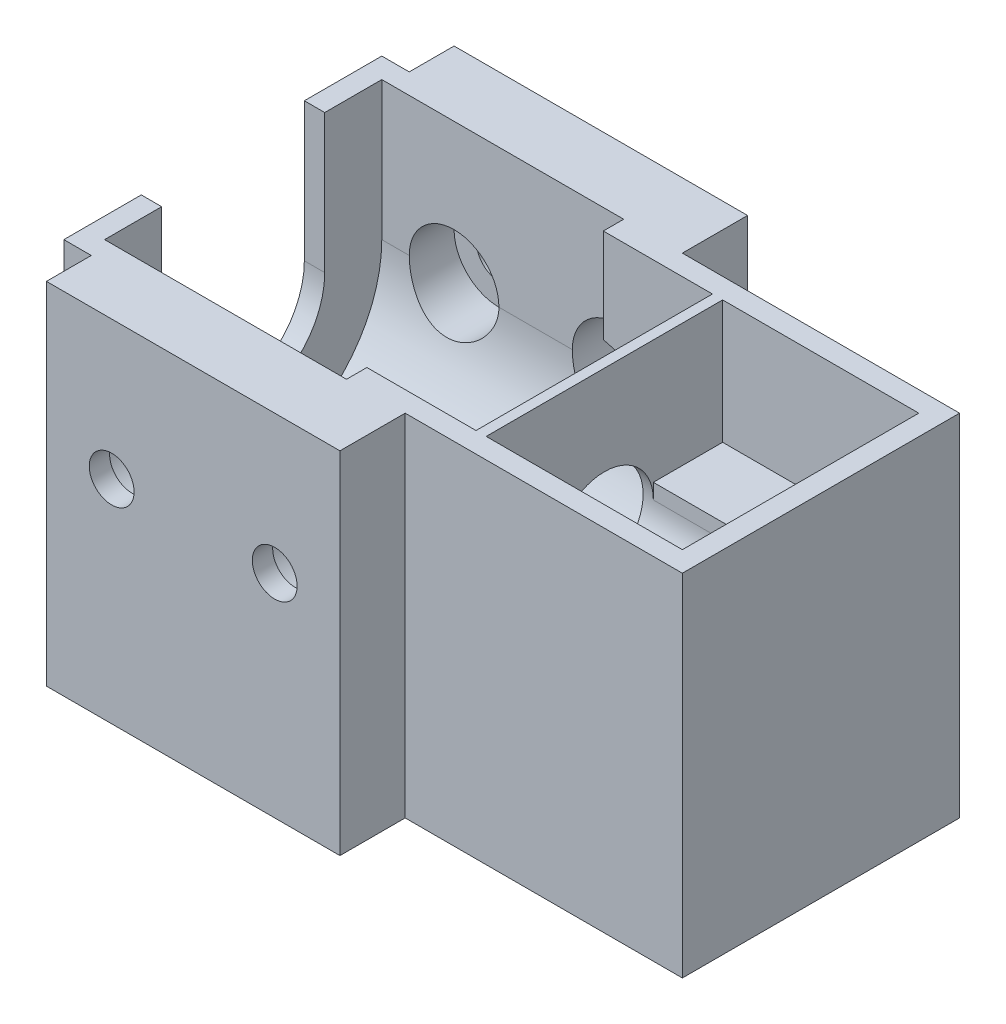
SolidWorks part; units mm, degrees
ref_plane "Front Plane" through (0, 0, 0) normal (0, 0, 1) x (1, 0, 0)
ref_plane "Top Plane" through (0, 0, 0) normal (0, 1, 0) x (1, 0, 0)
ref_plane "Right Plane" through (0, 0, 0) normal (1, 0, 0) x (0, 0, -1)
sketch "Sketch1" plane through (0, 0, 0) normal (0, 0, 1) x (1, 0, 0)
  line L1 (-76.2, -50.8) -> (40.64, -50.8)
  line L2 (-76.2, -50.8) -> (-76.2, 0)
  line L3 (-76.2, 0) -> (40.64, 0)
  line L4 (40.64, -50.8) -> (40.64, 0)
  line L5 (-76.2, -50.8) -> (40.64, 0) construction
  line L6 (-76.2, 0) -> (40.64, -50.8) construction
  point P0 (0, 0)
  dimension "D1" = 116.84
  dimension "D2" = 50.8
  dimension "D3" = 76.2
extrude "Boss-Extrude1" add sketch "Sketch1" along normal mid plane 63.5
sketch "Sketch2" plane through (0, 0, 0) normal (0, 0, 1) x (1, 0, 0)
  line L0 (-152.4829, -25.4) -> (6, -25.4) construction
  line L1 (-49.3609, -3.81) -> (-49.3609, -12.7)
  line L2 (40.64, 0) -> (-76.2, 0) construction
  line L3 (40.64, 0) -> (-76.2, 0) construction
  line L4 (-11.68, -3.81) -> (-11.68, -6.985)
  line L5 (-11.68, -25.4) -> (-11.68, -3.81) construction
  line L6 (-128.4172, -25.4) -> (-157.8092, -25.4)
  line L7 (6, -25.4) -> (40.64, -25.4)
  line L8 (-607.3619, -25.4) -> (6, -25.4) construction
  line L9 (-49.3609, -3.81) -> (-11.68, -3.81)
  line L10 (6, -25.4) -> (-128.4172, -25.4)
  line L11 (-11.68, -6.985) -> (5.32, -6.985)
  line L12 (5.32, -6.985) -> (5.32, -17.78)
  line L13 (5.32, -17.78) -> (23.32, -17.78)
  line L14 (-49.3609, -12.7) -> (-220.2024, -12.7)
  line L15 (-220.2024, -12.7) -> (-220.2024, -25.4)
  line L16 (-220.2024, -25.4) -> (-157.8092, -25.4)
  line L17 (23.32, -17.78) -> (23.32, -25.4) construction
  line L18 (23.32, -17.78) -> (40.64, -17.78)
  line L19 (40.64, -50.8) -> (40.64, 0) construction
  line L20 (40.64, -17.78) -> (40.64, -25.4)
  line L21 (-76.2, 0) -> (-76.2, -50.8) construction
  point P23 (-11.68, -25.4)
  dimension "D1" = 21.59
  dimension "D2" = 37.6809
  dimension "D3" = 25.4
  dimension "D4" = 35
  dimension "D5" = 7.62
  dimension "D6" = 3.175
  dimension "D7" = 26.8391
  dimension "D8" = 18
  dimension "D9" = 12.7
revolve "Cut-Revolve1" cut sketch "Sketch2" angle 360 about L0
sketch "Sketch38" plane through (40.64, 0, 0) normal (1, 0, 0) x (0, 0, -1)
  line L1 (-10, -35.4) -> (10, -35.4)
  line L2 (-10, -35.4) -> (-10, -15.4)
  line L3 (-10, -15.4) -> (10, -15.4)
  line L4 (10, -35.4) -> (10, -15.4)
  line L5 (-10, -35.4) -> (10, -15.4) construction
  line L6 (-10, -15.4) -> (10, -35.4) construction
  point P0 (0, -25.4)
  point P1 (0, -25.4)
  dimension "D1" = 20
  dimension "D2" = 20
extrude "Cut-Extrude33" cut sketch "Sketch38" against normal offset from surface (33.7325 mm away) 1.5875 up to face at (5.32, -43.815, 0)
sketch "Sketch37" plane through (40.64, 0, 0) normal (1, 0, 0) x (0, 0, -1)
  line L0 (31.75, -50.8) -> (31.75, 0) construction
  line L1 (-31.75, 0) -> (31.75, 0)
  line L2 (-31.75, 0) -> (-31.75, -25.4)
  line L3 (-31.75, -25.4) -> (31.75, -25.4)
  line L4 (31.75, 0) -> (31.75, -25.4)
  line L5 (10, -35.4) -> (10, -15.4) construction
  point P7 (0, -25.4)
  point P11 (0, 0)
  point P14 (10, -25.4)
extrude "Cut-Extrude32" cut sketch "Sketch37" against normal through all
sketch "Sketch39" plane through (0, -25.4, 0) normal (0, 1, 0) x (1, 0, 0)
  line L10 (-76.2, 12.7) -> (-49.3609, 12.7)
  line L11 (-49.3609, 12.7) -> (-49.3609, 21.59)
  line L12 (-49.3609, 21.59) -> (-11.68, 21.59)
  line L13 (-11.68, 21.59) -> (-11.68, 18.415)
  line L14 (-11.68, 18.415) -> (5.32, 18.415)
  line L15 (5.32, 18.415) -> (5.32, 7.62)
  line L16 (5.32, 18.415) -> (5.32, 7.62)
  line L17 (40.64, 10) -> (40.64, 31.75)
  line L18 (40.64, 31.75) -> (-76.2, 31.75)
  line L19 (-76.2, 31.75) -> (-76.2, 12.7)
  line L20 (-76.2, 12.7) -> (-49.3609, 12.7)
  line L21 (-49.3609, 12.7) -> (-49.3609, 21.59)
  line L22 (-49.3609, 21.59) -> (-11.68, 21.59)
  line L23 (-11.68, 21.59) -> (-11.68, 18.415)
  line L24 (-11.68, 18.415) -> (5.32, 18.415)
  line L25 (6.9075, 10) -> (40.64, 10)
  line L26 (6.9075, 10) -> (40.64, 10)
  line L27 (40.64, 10) -> (40.64, 31.75)
  line L28 (40.64, 31.75) -> (-76.2, 31.75)
  line L29 (-76.2, 31.75) -> (-76.2, 12.7)
  line L30 (-49.3609, -12.7) -> (-76.2, -12.7)
  line L31 (-76.2, -12.7) -> (-76.2, -31.75)
  line L32 (-76.2, -31.75) -> (40.64, -31.75)
  line L33 (40.64, -31.75) -> (40.64, -10)
  line L34 (40.64, -10) -> (6.9075, -10)
  line L35 (40.64, -10) -> (6.9075, -10)
  line L36 (5.32, -18.415) -> (-11.68, -18.415)
  line L37 (-11.68, -18.415) -> (-11.68, -21.59)
  line L38 (-11.68, -21.59) -> (-49.3609, -21.59)
  line L39 (-49.3609, -21.59) -> (-49.3609, -12.7)
  line L40 (-49.3609, -12.7) -> (-76.2, -12.7)
  line L41 (-76.2, -12.7) -> (-76.2, -31.75)
  line L42 (-76.2, -31.75) -> (40.64, -31.75)
  line L43 (40.64, -31.75) -> (40.64, -10)
  line L44 (5.32, -7.62) -> (5.32, -18.415)
  line L45 (5.32, -7.62) -> (5.32, -18.415)
  line L46 (5.32, -18.415) -> (-11.68, -18.415)
  line L47 (-11.68, -18.415) -> (-11.68, -21.59)
  line L48 (-11.68, -21.59) -> (-49.3609, -21.59)
  line L49 (-49.3609, -21.59) -> (-49.3609, -12.7)
  line L52 (5.32, 7.62) -> (6.9075, 7.62)
  line L53 (5.32, 7.62) -> (6.9075, 7.62)
  line L54 (6.9075, 7.62) -> (6.9075, 10)
  line L55 (6.9075, 7.62) -> (6.9075, 10)
  line L56 (6.9075, -10) -> (6.9075, -7.62)
  line L57 (6.9075, -10) -> (6.9075, -7.62)
  line L58 (6.9075, -7.62) -> (5.32, -7.62)
  line L59 (6.9075, -7.62) -> (5.32, -7.62)
  dimension "D1" = 0
  dimension "D2" = 0
extrude "Boss-Extrude5" add sketch "Sketch39" along normal blind 25.4
sketch "Sketch40" plane through (0, 0, 0) normal (0, 1, 0) x (1, 0, 0)
  line L0 (6.9075, 10) -> (40.64, 10) construction
  line L1 (23.32, 10) -> (40.64, 10)
  line L2 (23.32, 10) -> (23.32, -10)
  line L3 (23.32, -10) -> (40.64, -10)
  line L4 (40.64, 10) -> (40.64, -10)
  line L6 (-11.68, 21.59) -> (-11.68, 18.415) construction
  dimension "D1" = 35
extrude "Boss-Extrude6" add sketch "Sketch40" against normal up to next
sketch "Sketch41" plane through (0, 0, 0) normal (0, 1, 0) x (1, 0, 0)
  line L2 (-76.2, 12.7) -> (-76.2, -12.7) construction
  circle A0 centre (-57.15, 0) radius 3.1134
  circle A1 centre (-31.75, 0) radius 3.1134
  circle A2 centre (-6.35, 0) radius 3.1134
  dimension "D1" = 19.05
extrude "Cut-Extrude34" cut sketch "Sketch41" against normal through all
ref_plane "Plane_Mid" through (0, -25.4, 0) normal (0, 1, 0) x (1, 0, 0)
ref_axis "Axis1" through (6.9075, -25.4, 0) along (-1, 0, 0)
sketch "Sketch42" plane through (0, 0, 0) normal (0, 0, 1) x (1, 0, 0)
  line L0 (1.7462, -25.4) -> (-1.7462, -25.4) construction
  line L1 (-76.2, 0) -> (-76.2, -25.4) construction
  circle A0 centre (-38.1, -25.4) radius 3.4925
  circle A1 centre (-12.7, -25.4) radius 3.4925
  dimension "D1" = 6.985
  dimension "D2" = 38.1
extrude "Cut-Extrude35" cut sketch "Sketch42" against normal through all both and the other way through all
sketch "Sketch43" plane through (0, 0, 0) normal (0, 0, 1) x (1, 0, 0)
  circle A0 centre (-38.1, -25.4) radius 6.985
  circle A1 centre (-12.7, -25.4) radius 6.985
  dimension "D1" = 13.97
extrude "Cut-Extrude36" cut sketch "Sketch43" against normal offset from surface (28.575 mm away) 3.175 up to face at (-9.2075, -25.4, -31.75)
extrude "Cut-Extrude37" cut sketch "Sketch43<2>" along normal offset from surface (28.575 mm away) 3.175 up to face at (-9.2075, -25.4, 31.75)
sketch "Sketch43<2>" plane through (0, 0, 0) normal (0, 0, 1) x (1, 0, 0) same geometry as "Sketch43"
sketch "Sketch44" plane through (0, 0, 0) normal (0, 1, 0) x (1, 0, 0)
  line L0 (5.32, -18.415) -> (-11.68, -18.415) construction
  line L1 (6.9075, 18.415) -> (22.82, 18.415)
  line L2 (6.9075, 18.415) -> (6.9075, -18.415)
  line L3 (6.9075, -18.415) -> (22.82, -18.415)
  line L4 (22.82, 18.415) -> (22.82, -18.415)
  line L5 (-11.68, 18.415) -> (5.32, 18.415) construction
  line L6 (6.9075, 7.62) -> (6.9075, 10) construction
  line L7 (23.32, 10) -> (23.32, -10) construction
  dimension "D1" = 0.5
extrude "Cut-Extrude38" cut sketch "Sketch44" against normal up to surface (35.4 mm away) up to face at (15.1138, -35.4, 0)
sketch "Sketch45" plane through (0, 0, 0) normal (0, 0, 1) x (1, 0, 0)
  line L0 (40.64, 0) -> (-76.2, 0) construction
  line L2 (37.465, 0) -> (22.82, 0)
  line L4 (37.465, 0) -> (37.465, -15.4)
  line L5 (37.465, -15.4) -> (22.82, -15.4)
  line L8 (22.82, 0) -> (22.82, -15.4)
  line L9 (40.64, -50.8) -> (40.64, 0) construction
  line L10 (22.82, -35.4) -> (22.82, 0) construction
  line L11 (-5.715, -25.4) -> (5.32, -25.4) construction
  dimension "D1" = 3.175
  dimension "D2" = 10
extrude "Cut-Extrude39" cut sketch "Sketch45" against normal up to surface and the other way up to surface up to face at (14.8637, -17.7, -18.415) other way up to face at (14.8638, -17.7, 18.415)
sketch "Sketch46" plane through (0, 0, 0) normal (0, 1, 0) x (1, 0, 0)
  line L0 (-11.68, 18.415) -> (5.32, 18.415) construction
  line L1 (40.64, 31.75) -> (-2.54, 31.75)
  line L2 (40.64, 31.75) -> (40.64, 21.59)
  line L3 (40.64, 21.59) -> (-2.54, 21.59)
  line L4 (-2.54, 31.75) -> (-2.54, 21.59)
  line L5 (-76.2, 0) -> (40.64, 0) construction
  line L6 (-76.2, 12.7) -> (-76.2, -12.7) construction
  line L7 (40.64, -31.75) -> (40.64, 31.75) construction
  line L8 (40.64, -31.75) -> (40.64, -21.59)
  line L9 (40.64, -21.59) -> (-2.54, -21.59)
  line L10 (40.64, -31.75) -> (-2.54, -31.75)
  line L11 (-2.54, -31.75) -> (-2.54, -21.59)
  line L12 (-49.3609, 21.59) -> (-11.68, 21.59) construction
  line L13 (-76.2, 31.75) -> (-48.26, 31.75)
  line L14 (-76.2, 31.75) -> (-76.2, 24.765)
  line L15 (-76.2, 24.765) -> (-48.26, 24.765)
  line L16 (-48.26, 31.75) -> (-48.26, 24.765)
  line L17 (-48.26, -31.75) -> (-48.26, -24.765)
  line L18 (-76.2, -24.765) -> (-48.26, -24.765)
  line L19 (-76.2, -31.75) -> (-76.2, -24.765)
  line L20 (-76.2, -31.75) -> (-48.26, -31.75)
  dimension "D1" = 3.175
  dimension "D2" = 3.175
  dimension "D3" = 3.175
  dimension "D4" = 3.175
extrude "Cut-Extrude40" cut sketch "Sketch46" against normal through all
sketch "Sketch49" plane through (0, 0, 0) normal (0, 1, 0) x (1, 0, 0)
  line L0 (-48.26, -24.765) -> (-76.2, -24.765) construction
  line L1 (-76.2, 24.765) -> (-52.5359, 24.765)
  line L2 (-76.2, 24.765) -> (-76.2, -24.765)
  line L3 (-76.2, -24.765) -> (-52.5359, -24.765)
  line L4 (-52.5359, 24.765) -> (-52.5359, -24.765)
  line L5 (-49.3609, -21.59) -> (-49.3609, 21.59) construction
  dimension "D1" = 3.175
extrude "Cut-Extrude42" cut sketch "Sketch49" against normal through all
sketch "Sketch50" plane through (0, 0, 0) normal (0, 1, 0) x (1, 0, 0)
  line L0 (-2.54, 21.59) -> (40.64, 21.59) construction
  line L1 (22.566, 20.066) -> (22.82, 20.066)
  line L2 (22.566, 20.066) -> (22.566, 21.59)
  line L3 (22.566, 21.59) -> (22.82, 21.59)
  line L4 (22.82, 20.066) -> (22.82, 21.59)
  line L5 (22.693, 21.59) -> (22.693, 20.066) construction
  line L6 (22.566, 20.828) -> (22.82, 20.828) construction
  line L8 (22.82, 10) -> (22.82, 18.415) construction
  line L9 (21.042, 20.066) -> (21.296, 20.066)
  line L10 (21.296, 20.066) -> (21.296, 21.59)
  line L11 (21.042, 21.59) -> (21.296, 21.59)
  line L12 (21.042, 20.066) -> (21.042, 21.59)
  line L13 (19.518, 20.066) -> (19.772, 20.066)
  line L14 (19.772, 20.066) -> (19.772, 21.59)
  line L15 (19.518, 21.59) -> (19.772, 21.59)
  line L16 (19.518, 20.066) -> (19.518, 21.59)
  line L17 (17.994, 20.066) -> (18.248, 20.066)
  line L18 (18.248, 20.066) -> (18.248, 21.59)
  line L19 (17.994, 21.59) -> (18.248, 21.59)
  line L20 (17.994, 20.066) -> (17.994, 21.59)
  line L21 (16.47, 20.066) -> (16.724, 20.066)
  line L22 (16.724, 20.066) -> (16.724, 21.59)
  line L23 (16.47, 21.59) -> (16.724, 21.59)
  line L24 (16.47, 20.066) -> (16.47, 21.59)
  line L25 (14.946, 20.066) -> (15.2, 20.066)
  line L26 (15.2, 20.066) -> (15.2, 21.59)
  line L27 (14.946, 21.59) -> (15.2, 21.59)
  line L28 (14.946, 20.066) -> (14.946, 21.59)
  line L29 (13.422, 20.066) -> (13.676, 20.066)
  line L30 (13.676, 20.066) -> (13.676, 21.59)
  line L31 (13.422, 21.59) -> (13.676, 21.59)
  line L32 (13.422, 20.066) -> (13.422, 21.59)
  line L33 (11.898, 20.066) -> (12.152, 20.066)
  line L34 (12.152, 20.066) -> (12.152, 21.59)
  line L35 (11.898, 21.59) -> (12.152, 21.59)
  line L36 (11.898, 20.066) -> (11.898, 21.59)
  line L37 (10.374, 20.066) -> (10.628, 20.066)
  line L38 (10.628, 20.066) -> (10.628, 21.59)
  line L39 (10.374, 21.59) -> (10.628, 21.59)
  line L40 (10.374, 20.066) -> (10.374, 21.59)
  line L41 (8.85, 20.066) -> (9.104, 20.066)
  line L42 (9.104, 20.066) -> (9.104, 21.59)
  line L43 (8.85, 21.59) -> (9.104, 21.59)
  line L44 (8.85, 20.066) -> (8.85, 21.59)
  point P0 (22.693, 20.828)
  dimension "D1" = 0.254
  dimension "D2" = 1.524
  dimension "D3" = 10
extrude "Cut-Extrude43" cut sketch "Sketch50" against normal blind 2.54
sketch "Sketch52" plane through (23.32, 0, 0) normal (-1, 0, 0) x (0, 0, 1)
  circle A0 centre (0, -25.4) radius 0.3175
  dimension "D1" = 0.635
extrude "Cut-Extrude45" cut sketch "Sketch52" against normal blind 0.0508
sketch "Sketch53" plane through (23.32, 0, 0) normal (-1, 0, 0) x (0, 0, 1)
  circle A0 centre (0, -25.4) radius 2
  dimension "D1" = 4
extrude "Cut-Extrude46" cut sketch "Sketch53" against normal blind 0.0254
sketch "Sketch54" plane through (0, -35.4, 0) normal (0, 1, 0) x (1, 0, 0)
  line L0 (22.82, 10) -> (22.82, -10)
  line L8 (23.32, 10) -> (22.82, 10)
  line L9 (22.82, 10) -> (22.82, 18.415)
  line L10 (22.82, 18.415) -> (6.9075, 18.415)
  line L11 (6.9075, 18.415) -> (6.9075, -18.415)
  line L12 (6.9075, -18.415) -> (22.82, -18.415)
  line L13 (22.82, -18.415) -> (22.82, -10)
  line L14 (22.82, -10) -> (23.32, -10)
  line L15 (23.32, -10) -> (23.32, 10)
  line L17 (22.82, 10) -> (22.82, 18.415)
  line L18 (22.82, 18.415) -> (6.9075, 18.415)
  line L19 (6.9075, 18.415) -> (6.9075, -18.415)
  line L20 (6.9075, -18.415) -> (22.82, -18.415)
  line L21 (22.82, -18.415) -> (22.82, -10)
  dimension "D1" = 0
extrude "Boss-Extrude7" add sketch "Sketch54" along normal blind 2.54
sketch "Sketch55" plane through (0, -32.86, 0) normal (0, 1, 0) x (1, 0, 0)
  line L0 (22.82, -18.415) -> (22.82, -10) construction
  line L1 (22.82, 10) -> (6.9075, 10)
  line L2 (22.82, 10) -> (22.82, 18.415)
  line L3 (22.82, 18.415) -> (6.9075, 18.415)
  line L4 (6.9075, 10) -> (6.9075, 18.415)
  line L5 (22.82, 10) -> (6.9075, 18.415) construction
  line L6 (22.82, 18.415) -> (6.9075, 10) construction
  line L7 (6.9075, -18.415) -> (22.82, -18.415)
  line L8 (6.9075, -18.415) -> (6.9075, -10)
  line L9 (6.9075, -10) -> (22.82, -10)
  line L10 (22.82, -18.415) -> (22.82, -10)
  line L11 (6.9075, -18.415) -> (22.82, -10) construction
  line L12 (6.9075, -10) -> (22.82, -18.415) construction
  point P4 (14.8637, 14.2075)
  point P5 (0, 0)
  point P11 (14.8637, -14.2075)
  point P15 (0, 0)
  point P17 (0, 0)
extrude "Boss-Extrude8" add sketch "Sketch55" along normal up to surface (17.46 mm away) up to face at (26.6063, -15.4, 0)
sketch "Sketch56" plane through (0, 0, 0) normal (0, 0, 1) x (1, 0, 0)
  line L0 (16.47, -27.4) -> (16.47, -32.86) construction
  line L1 (23.3454, -27.4) -> (16.47, -27.4) construction
  line L2 (23.3454, -23.4) -> (23.3454, -27.4) construction
  line L3 (6.9075, -25.4) -> (5.32, -25.4) construction
  line L4 (6.9075, -32.86) -> (6.9075, -25.4) construction
  line L5 (11.6888, -30.13) -> (6.9075, -30.13) construction
  line L6 (11.6888, -30.13) -> (16.47, -30.13) construction
  line L7 (16.47, -27.4) -> (22.82, -27.4)
  line L8 (22.82, -27.4) -> (22.82, -32.86)
  line L9 (6.9075, -32.86) -> (22.82, -32.86)
  spline S0 degree 3 poles (6.9075, -32.86) (7.8397, -32.86) (14.8054, -27.986) (15.1522, -27.4) (16.47, -27.4) knots 0 0 0 0 0.327131 1 1 1 1
  point P6 (16.47, -30.13)
  point P8 (0, 0)
  point P11 (6.9075, -32.86)
  dimension "D1" = 2
  dimension "D2" = 6.35
extrude "Boss-Extrude9" add sketch "Sketch56" along normal up to next and the other way up to next
sketch "Sketch57" plane through (0, -15.4, 0) normal (0, 1, 0) x (1, 0, 0)
  line L8 (23.32, -10) -> (6.9075, -10)
  line L9 (6.9075, -10) -> (6.9075, -18.415)
  line L10 (6.9075, -18.415) -> (37.465, -18.415)
  line L11 (37.465, -18.415) -> (37.465, 18.415)
  line L12 (37.465, 18.415) -> (6.9075, 18.415)
  line L13 (23.32, -10) -> (6.9075, -10)
  line L14 (6.9075, 18.415) -> (6.9075, 10)
  line L15 (23.32, 10) -> (23.32, -10)
  line L16 (6.9075, 18.415) -> (6.9075, 10)
  line L17 (6.9075, -10) -> (6.9075, -18.415)
  line L18 (6.9075, -18.415) -> (37.465, -18.415)
  line L19 (37.465, -18.415) -> (37.465, 18.415)
  line L20 (37.465, 18.415) -> (6.9075, 18.415)
  line L21 (6.9075, 10) -> (23.32, 10)
  line L22 (6.9075, 10) -> (23.32, 10)
  line L23 (23.32, 10) -> (23.32, -10)
  dimension "D1" = 0
extrude "Cut-Extrude47" cut sketch "Sketch57" against normal blind 7.62
sketch "Sketch58" plane through (0, -50.8, 0) normal (0, -1, 0) x (1, 0, 0)
  line L12 (-48.26, 24.765) -> (-52.5359, 24.765)
  line L13 (-52.5359, 24.765) -> (-52.5359, -24.765)
  line L14 (-52.5359, -24.765) -> (-48.26, -24.765)
  line L15 (-48.26, -24.765) -> (-48.26, -31.75)
  line L16 (-48.26, -31.75) -> (-2.54, -31.75)
  line L17 (-2.54, -31.75) -> (-2.54, -21.59)
  line L18 (-2.54, -21.59) -> (40.64, -21.59)
  line L19 (40.64, -21.59) -> (40.64, 21.59)
  line L20 (40.64, 21.59) -> (-2.54, 21.59)
  line L21 (-2.54, 21.59) -> (-2.54, 31.75)
  line L22 (-2.54, 31.75) -> (-48.26, 31.75)
  line L23 (-48.26, 31.75) -> (-48.26, 24.765)
  line L24 (-48.26, 24.765) -> (-52.5359, 24.765)
  line L25 (-52.5359, 24.765) -> (-52.5359, -24.765)
  line L26 (-52.5359, -24.765) -> (-48.26, -24.765)
  line L27 (-48.26, -24.765) -> (-48.26, -31.75)
  line L28 (-48.26, -31.75) -> (-2.54, -31.75)
  line L29 (-2.54, -31.75) -> (-2.54, -21.59)
  line L30 (-2.54, -21.59) -> (40.64, -21.59)
  line L31 (40.64, -21.59) -> (40.64, 21.59)
  line L32 (40.64, 21.59) -> (-2.54, 21.59)
  line L33 (-2.54, 21.59) -> (-2.54, 31.75)
  line L34 (-2.54, 31.75) -> (-48.26, 31.75)
  line L35 (-48.26, 31.75) -> (-48.26, 24.765)
  circle A0 centre (-31.75, 0) radius 3.1134
  circle A1 centre (-6.35, 0) radius 3.1134
  circle A2 centre (-6.35, 0) radius 3.1134 construction
  circle A3 centre (-31.75, 0) radius 3.1134 construction
  dimension "D1" = 0
extrude "Boss-Extrude10" add sketch "Sketch58" along normal blind 7.62
sketch "Sketch59" plane through (0, -35.4, 0) normal (0, 1, 0) x (1, 0, 0)
  line L4 (22.82, 10) -> (22.82, -10)
  line L5 (22.82, -10) -> (23.32, -10)
  line L6 (23.32, -10) -> (23.32, 10)
  line L7 (23.32, 10) -> (22.82, 10)
  line L8 (22.82, 10) -> (22.82, -10)
  line L9 (22.82, -10) -> (23.32, -10)
  line L10 (23.32, -10) -> (23.32, 10)
  line L11 (23.32, 10) -> (22.82, 10)
  dimension "D1" = 0
extrude "Cut-Extrude48" cut sketch "Sketch59" against normal blind 7.62
sketch "Sketch51" plane through (0, -23.02, 0) normal (0, 1, 0) x (1, 0, 0)
  line L0 (24.844, 0.127) -> (26.1082, 0.127)
  line L1 (24.59, 1.27) -> (24.844, 1.27)
  line L2 (24.59, 1.27) -> (24.59, 0.127)
  line L3 (24.59, -1.27) -> (24.844, -1.27)
  line L4 (24.844, 1.27) -> (24.844, 0.127)
  line L5 (29.3987, -0.127) -> (30.6629, -0.127)
  line L6 (24.844, -0.127) -> (24.844, -1.27)
  line L7 (26.3622, 1.27) -> (26.3622, 0.127)
  line L8 (26.1082, 1.27) -> (26.3622, 1.27)
  line L9 (26.1082, 1.27) -> (26.1082, 0.127)
  line L10 (26.1082, -1.27) -> (26.3622, -1.27)
  line L11 (27.8804, 1.27) -> (27.8804, 0.127)
  line L12 (27.6264, 1.27) -> (27.8804, 1.27)
  line L13 (27.6264, 1.27) -> (27.6264, 0.127)
  line L14 (27.6264, -1.27) -> (27.8804, -1.27)
  line L15 (29.3987, 1.27) -> (29.3987, 0.127)
  line L16 (29.1447, 1.27) -> (29.3987, 1.27)
  line L17 (29.1447, 1.27) -> (29.1447, 0.127)
  line L18 (29.1447, -1.27) -> (29.3987, -1.27)
  line L19 (30.9169, 1.27) -> (30.9169, 0.127)
  line L20 (30.6629, 1.27) -> (30.9169, 1.27)
  line L21 (30.6629, 1.27) -> (30.6629, 0.127)
  line L22 (30.6629, -1.27) -> (30.9169, -1.27)
  line L23 (32.4351, 1.27) -> (32.4351, 0.127)
  line L24 (32.1811, 1.27) -> (32.4351, 1.27)
  line L25 (32.1811, 1.27) -> (32.1811, 0.127)
  line L26 (32.1811, -1.27) -> (32.4351, -1.27)
  line L27 (33.9533, 1.27) -> (33.9533, 0.127)
  line L28 (33.6993, 1.27) -> (33.9533, 1.27)
  line L29 (33.6993, 1.27) -> (33.6993, 0.127)
  line L30 (33.6993, -1.27) -> (33.9533, -1.27)
  line L31 (35.4715, 1.27) -> (35.4715, 0.127)
  line L32 (35.2175, 1.27) -> (35.4715, 1.27)
  line L33 (35.2175, 1.27) -> (35.2175, 0.127)
  line L34 (35.2175, -1.27) -> (35.4715, -1.27)
  line L35 (35.258, 2.5876) -> (24.1619, 2.5876) construction
  line L36 (23.32, 11.7754) -> (37.465, 11.7754) construction
  line L37 (24.844, -0.127) -> (26.1082, -0.127)
  line L38 (23.32, 10) -> (23.32, -10) construction
  line L39 (37.465, -18.415) -> (37.465, 18.415) construction
  line L40 (23.32, 0.127) -> (24.59, 0.127)
  line L41 (23.32, 0.127) -> (23.32, -0.127)
  line L42 (23.32, -0.127) -> (24.59, -0.127)
  line L43 (37.465, 0.127) -> (37.465, -0.127)
  line L44 (30.9169, 0.127) -> (32.1811, 0.127)
  line L46 (24.59, -0.127) -> (24.59, -1.27)
  line L47 (26.1082, -0.127) -> (26.1082, -1.27)
  line L48 (26.3622, 0.127) -> (27.6264, 0.127)
  line L49 (26.3622, -0.127) -> (26.3622, -1.27)
  line L51 (26.3622, -0.127) -> (27.6264, -0.127)
  line L52 (27.6264, -0.127) -> (27.6264, -1.27)
  line L53 (27.8804, 0.127) -> (29.1447, 0.127)
  line L54 (27.8804, -0.127) -> (29.1447, -0.127)
  line L55 (27.8804, -0.127) -> (27.8804, -1.27)
  line L56 (29.1447, -0.127) -> (29.1447, -1.27)
  line L57 (29.3987, 0.127) -> (30.6629, 0.127)
  line L58 (30.9169, -0.127) -> (32.1811, -0.127)
  line L61 (29.3987, -0.127) -> (29.3987, -1.27)
  line L62 (30.6629, -0.127) -> (30.6629, -1.27)
  line L63 (30.9169, -0.127) -> (30.9169, -1.27)
  line L64 (32.1811, -0.127) -> (32.1811, -1.27)
  line L65 (32.4351, 0.127) -> (33.6993, 0.127)
  line L66 (32.4351, -0.127) -> (33.6993, -0.127)
  line L67 (32.4351, -0.127) -> (32.4351, -1.27)
  line L68 (33.6993, -0.127) -> (33.6993, -1.27)
  line L69 (33.9533, 0.127) -> (35.2175, 0.127)
  line L70 (33.9533, -0.127) -> (35.2175, -0.127)
  line L71 (33.9533, -0.127) -> (33.9533, -1.27)
  line L72 (35.2175, -0.127) -> (35.2175, -1.27)
  line L73 (35.4715, -0.127) -> (35.4715, -1.27)
  line L74 (35.4715, 0.127) -> (37.465, 0.127)
  line L75 (35.4715, -0.127) -> (37.465, -0.127)
  text T0 "<b>494 kHz WL/2</b>" font "Century Gothic" height 1.27
  text T1 "<b>v5</b>"
  point P0 (24.717, 0)
  point P51 (30.3925, 0)
  point P52 (23.32, 0)
  dimension "D1" = 0.254
  dimension "D2" = 2.54
  dimension "D3" = 1.5182
  dimension "D5" = 0.8419
  dimension "D6" = 0.254
  dimension "D4" = 8
extrude "Cut-Extrude44" cut sketch "Sketch51" against normal blind 0.635
sketch "Sketch60" plane through (0, 0, 0) normal (0, 1, 0) x (1, 0, 0)
  line L1 (-60.6783, -40.5295) -> (60.6783, -40.5295)
  line L2 (-60.6783, -40.5295) -> (-60.6783, 40.5295)
  line L3 (-60.6783, 40.5295) -> (60.6783, 40.5295)
  line L4 (60.6783, -40.5295) -> (60.6783, 40.5295)
  line L5 (0, 40.5295) -> (0, -40.5295) construction
  line L6 (-60.6783, 0) -> (60.6783, 0) construction
  point P0 (0, 0)
extrude "Cut-Extrude49" cut sketch "Sketch60" against normal blind 10.16
ref_plane "Plane_Bottom" through (0, -46.99, 0) normal (0, 1, 0) x (1, 0, 0)
ref_plane "Plane_Top" through (0, -3.81, 0) normal (0, 1, 0) x (1, 0, 0)
sketch "Sketch61" plane through (5.32, 0, 0) normal (-1, 0, 0) x (0, 0, 1)
  circle A0 centre (0, -25.4) radius 7.62
  circle A1 centre (0, -25.4) radius 8.9762
extrude "Boss-Extrude11" add sketch "Sketch61" against normal up to surface (1.5875 mm away) up to face at (6.9075, -21.9643, -11.5543)
sketch "Sketch62" plane through (0, -10.16, 0) normal (0, 1, 0) x (1, 0, 0)
  line L1 (6.9075, 7.62) -> (5.32, 7.62)
  line L2 (6.9075, 7.62) -> (6.9075, -7.62)
  line L3 (6.9075, -7.62) -> (5.32, -7.62)
  line L4 (5.32, 7.62) -> (5.32, -7.62)
  line L5 (6.9075, 7.62) -> (5.32, -7.62) construction
  line L6 (6.9075, -7.62) -> (5.32, 7.62) construction
  point P4 (6.1137, 0)
extrude "Boss-Extrude12" add sketch "Sketch62" against normal up to next
sketch "Sketch64" plane through (0, -10.16, 0) normal (0, 1, 0) x (1, 0, 0)
  line L25 (37.465, 18.415) -> (6.9075, 18.415)
  line L26 (37.465, 18.415) -> (37.465, -18.415)
  line L27 (37.465, -18.415) -> (6.9075, -18.415)
  line L28 (6.9075, 18.415) -> (6.9075, -18.415)
  line L29 (37.465, 18.415) -> (6.9075, -18.415) construction
  line L30 (37.465, -18.415) -> (6.9075, 18.415) construction
  line L48 (-11.68, 18.415) -> (5.32, 18.415)
  line L49 (5.32, 18.415) -> (5.32, -18.415)
  line L50 (5.32, -18.415) -> (-11.68, -18.415)
  line L51 (-11.68, -18.415) -> (-11.68, -21.59)
  line L52 (-11.68, -21.59) -> (-49.3609, -21.59)
  line L53 (-49.3609, -21.59) -> (-49.3609, -12.7)
  line L54 (-49.3609, -12.7) -> (-52.5359, -12.7)
  line L55 (-52.5359, -12.7) -> (-52.5359, -24.765)
  line L56 (-52.5359, -24.765) -> (-48.26, -24.765)
  line L57 (-48.26, -24.765) -> (-48.26, -31.75)
  line L58 (-48.26, -31.75) -> (-2.54, -31.75)
  line L59 (-2.54, -31.75) -> (-2.54, -21.59)
  line L60 (-2.54, -21.59) -> (40.64, -21.59)
  line L61 (40.64, -21.59) -> (40.64, 21.59)
  line L62 (40.64, 21.59) -> (-2.54, 21.59)
  line L63 (-2.54, 21.59) -> (-2.54, 31.75)
  line L64 (-2.54, 31.75) -> (-48.26, 31.75)
  line L65 (-48.26, 31.75) -> (-48.26, 24.765)
  line L66 (-48.26, 24.765) -> (-52.5359, 24.765)
  line L67 (-52.5359, 24.765) -> (-52.5359, 12.7)
  line L68 (-52.5359, 12.7) -> (-49.3609, 12.7)
  line L69 (-49.3609, 12.7) -> (-49.3609, 21.59)
  line L70 (-49.3609, 21.59) -> (-11.68, 21.59)
  line L71 (-11.68, 21.59) -> (-11.68, 18.415)
  line L72 (-11.68, 18.415) -> (5.32, 18.415)
  line L73 (5.32, 18.415) -> (5.32, -18.415)
  line L74 (5.32, -18.415) -> (-11.68, -18.415)
  line L75 (-11.68, -18.415) -> (-11.68, -21.59)
  line L76 (-11.68, -21.59) -> (-49.3609, -21.59)
  line L77 (-49.3609, -21.59) -> (-49.3609, -12.7)
  line L78 (-49.3609, -12.7) -> (-52.5359, -12.7)
  line L79 (-52.5359, -12.7) -> (-52.5359, -24.765)
  line L80 (-52.5359, -24.765) -> (-48.26, -24.765)
  line L81 (-48.26, -24.765) -> (-48.26, -31.75)
  line L82 (-48.26, -31.75) -> (-2.54, -31.75)
  line L83 (-2.54, -31.75) -> (-2.54, -21.59)
  line L84 (-2.54, -21.59) -> (40.64, -21.59)
  line L85 (40.64, -21.59) -> (40.64, 21.59)
  line L86 (40.64, 21.59) -> (-2.54, 21.59)
  line L87 (-2.54, 21.59) -> (-2.54, 31.75)
  line L88 (-2.54, 31.75) -> (-48.26, 31.75)
  line L89 (-48.26, 31.75) -> (-48.26, 24.765)
  line L90 (-48.26, 24.765) -> (-52.5359, 24.765)
  line L91 (-52.5359, 24.765) -> (-52.5359, 12.7)
  line L92 (-52.5359, 12.7) -> (-49.3609, 12.7)
  line L93 (-49.3609, 12.7) -> (-49.3609, 21.59)
  line L94 (-49.3609, 21.59) -> (-11.68, 21.59)
  line L95 (-11.68, 21.59) -> (-11.68, 18.415)
  point P28 (22.1862, 0)
  dimension "D1" = 0
extrude "Boss-Extrude14" add sketch "Sketch64" along normal up to surface (6.35 mm away) up to plane "Plane_Top"
sketch "Sketch66" plane through (0, -23.02, 0) normal (0, 1, 0) x (1, 0, 0)
  line L1 (23.32, 10) -> (22.82, 10)
  line L2 (23.32, 10) -> (23.32, -10)
  line L3 (23.32, -10) -> (22.82, -10)
  line L4 (22.82, 10) -> (22.82, -10)
  line L5 (23.32, 10) -> (22.82, -10) construction
  line L6 (23.32, -10) -> (22.82, 10) construction
  line L7 (22.82, 10) -> (22.82, -10) construction
  line L9 (6.9075, 0) -> (5.32, 0) construction
  line L10 (23.32, -0.127) -> (23.32, -10) construction
  point P4 (23.07, 0)
  point P6 (0, 0)
  point P7 (0, 0)
  point P10 (0, 0)
  point P15 (22.685, -3.5933)
  dimension "D1" = 20
extrude "Cut-Extrude50" [suppressed] cut sketch "Sketch66" against normal up to surface (20 mm away)
sketch "Sketch65" plane through (6.9075, 0, 0) normal (1, 0, 0) x (0, 0, -1)
  line L0 (-10, -23.02) -> (-7.62, -23.02)
  line L1 (10, -23.02) -> (7.62, -23.02)
  line L2 (-7.62, -25.4) -> (-7.62, -23.02)
  line L3 (7.62, -25.4) -> (7.62, -23.02)
  line L6 (-10, -23.02) -> (-10, -32.86)
  line L7 (-10, -32.86) -> (-1.5533, -32.86)
  line L8 (1.5533, -32.86) -> (10, -32.86)
  line L9 (18.415, -23.02) -> (18.415, -3.81)
  line L10 (18.415, -3.81) -> (-18.415, -3.81)
  line L11 (-18.415, -3.81) -> (-18.415, -23.02)
  line L12 (-18.415, -23.02) -> (-10, -23.02)
  line L13 (-10, -23.02) -> (-10, -32.86)
  line L15 (-10, -32.86) -> (-1.5533, -32.86)
  line L25 (1.5533, -32.86) -> (10, -32.86)
  line L27 (10, -32.86) -> (10, -23.02)
  line L28 (10, -32.86) -> (10, -23.02)
  line L29 (10, -23.02) -> (18.415, -23.02)
  arc A0 (-7.62, -25.4) -> (-1.5533, -32.86) centre (0, -25.4) ccw
  arc A1 (1.5533, -32.86) -> (-1.5533, -32.86) centre (0, -25.4) ccw
  arc A2 (1.5533, -32.86) -> (7.62, -25.4) centre (0, -25.4) ccw
  point P12 (8.81, -23.02)
  dimension "D1" = 0
extrude "Boss-Extrude16" add sketch "Sketch65" along normal up to next
